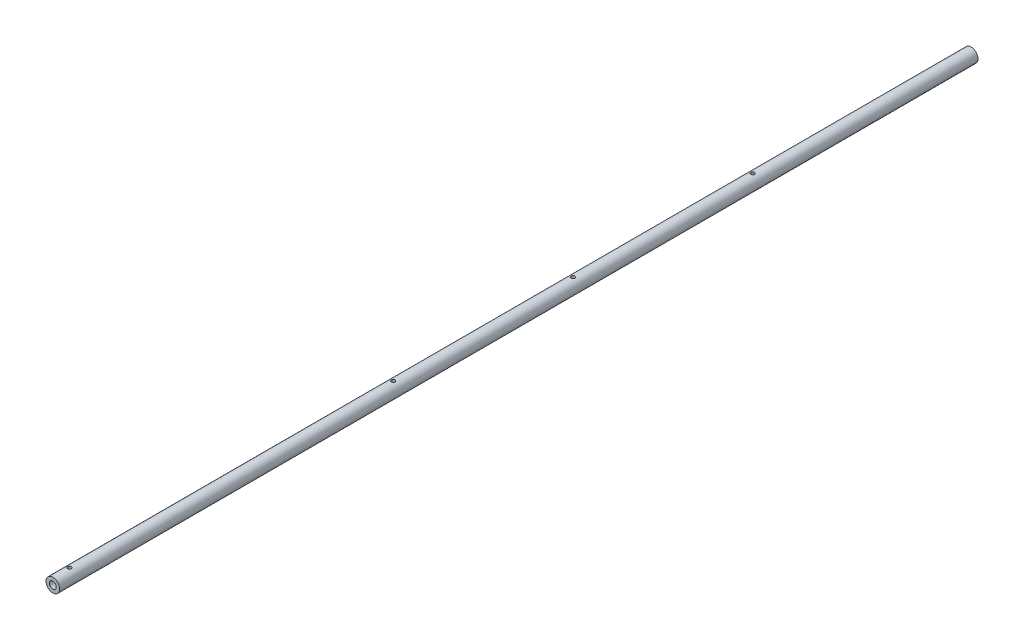
SolidWorks part; units mm, degrees
ref_plane "Front Plane" through (0, 0, 0) normal (0, 0, 1) x (1, 0, 0)
ref_plane "Top Plane" through (0, 0, 0) normal (0, 1, 0) x (1, 0, 0)
ref_plane "Right Plane" through (0, 0, 0) normal (1, 0, 0) x (0, 0, -1)
sketch "Sketch1" plane through (0, 0, 0) normal (0, 0, 1) x (1, 0, 0)
  circle A0 centre (0, 0) radius 3.9306
  circle A1 centre (0, 0) radius 7.8613
  dimension "D1" = 15.7226
  dimension "D2" = 7.8613
extrude "Rod" add sketch "Sketch1" along normal blind 1054.1
sketch "Sketch3" plane through (0, 0, 0) normal (0, 1, 0) x (1, 0, 0)
  line L0 (0, -663.575) -> (0, -1028.7) construction
  line L1 (-7.8613, -1054.1) -> (7.8613, -1054.1) construction
  circle A0 centre (0, -250.825) radius 2.1082
  circle A4 centre (0, -457.2) radius 2.1082
  circle A8 centre (0, -663.575) radius 2.1082
  circle A9 centre (0, -1035.05) radius 2.1082
  dimension "D1" = 4.2164
  dimension "D6" = 4.2164
  dimension "D2" = 250.825
  dimension "D4" = 206.375
  dimension "D5" = 365.125
  dimension "D7" = 19.05
  dimension "D3" = 3
extrude "Holes" cut sketch "Sketch3" against normal through all both and the other way through all
ref_plane "Handle Location" through (0, 0, 1028.7) normal (0, 0, 1) x (1, 0, 0)
equation "\"L\"= 41.5"
equation "\"D1@Rod\" = \"L\""
equation "\"N\"= 3"
equation "\"D3@Sketch3\"=\"N\""
equation "\"S\"= 8.125"
equation "\"D4@Sketch3\"=\"S\""
equation "\"O\"= 9.875"
equation "\"D2@Sketch3\"=\"O\""
equation "\"H\"= 14.375"
equation "\"D5@Sketch3\"=\"H\""
